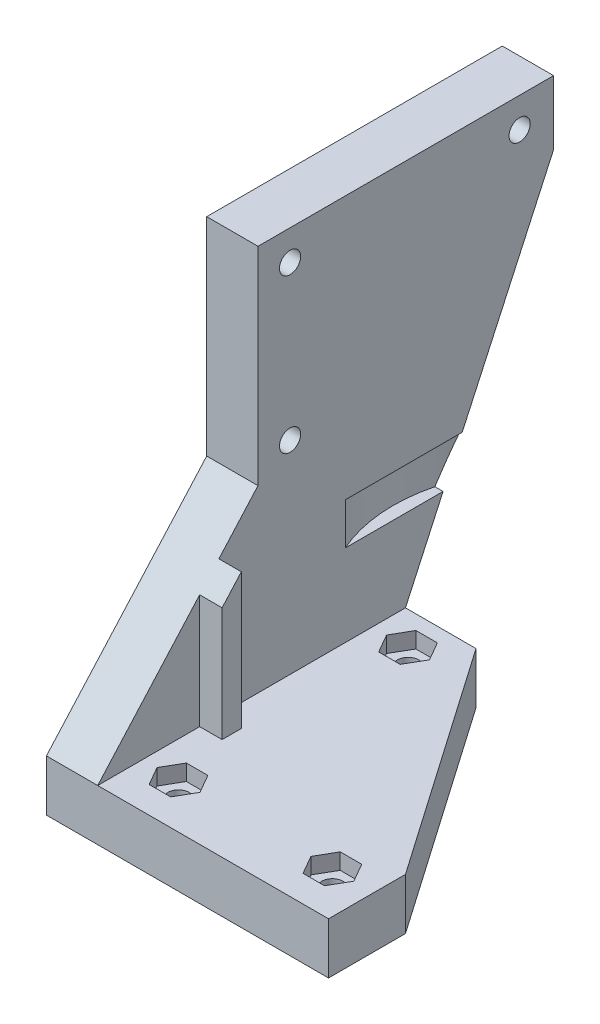
SolidWorks part; units mm, degrees
material "Copper"
ref_plane "Front Plane" through (0, 0, 0) normal (0, 0, 1) x (1, 0, 0)
ref_plane "Top Plane" through (0, 0, 0) normal (0, 1, 0) x (1, 0, 0)
ref_plane "Right Plane" through (0, 0, 0) normal (1, 0, 0) x (0, 0, -1)
sketch "Sketch1" plane through (0, 0, 0) normal (0, 1, 0) x (1, 0, 0)
  line L0 (-30.2016, 21.4588) -> (-19.2016, 21.4588)
  line L1 (5.7984, -26.5412) -> (5.7984, -14.5412)
  line L2 (-30.2016, 21.4588) -> (-30.2016, -26.5412)
  line L3 (-30.2016, -26.5412) -> (5.7984, -26.5412)
  line L4 (5.7984, -14.5412) -> (-19.2016, 21.4588)
  circle A0 centre (-24.6516, 16.3088) radius 1.65
  circle A1 centre (-24.6516, -19.4912) radius 1.65
  circle A2 centre (-0.6516, -19.4912) radius 1.65
  dimension "D3" = 3.3
  dimension "D6" = 3.3
  dimension "D9" = 3.3
  dimension "D1" = 48
  dimension "D2" = 5.15
  dimension "D4" = 5.55
  dimension "D5" = 11
  dimension "D7" = 35.8
  dimension "D8" = 5.55
  dimension "D10" = 24
  dimension "D11" = 35.8
  dimension "D12" = 12
extrude "Boss-Extrude1" add sketch "Sketch1" along normal blind 8
sketch "Sketch3" plane through (-30.2016, 0, 0) normal (-1, 0, 0) x (0, 0, 1)
  line L0 (-21.4588, 8) -> (26.5412, 8) construction
  line L1 (-44.5588, 58.3345) -> (-21.4588, 8)
  line L5 (26.5412, 8) -> (26.5412, 0) construction
  line L7 (-21.4588, 0) -> (26.5412, 0)
  line L8 (26.5412, 0) -> (26.5412, 8)
  line L9 (26.5412, 8) -> (1.5412, 36)
  line L10 (1.5412, 36) -> (1.5412, 68.3345)
  line L11 (1.5412, 68.3345) -> (-44.5588, 68.3345)
  line L12 (-44.5588, 68.3345) -> (-44.5588, 58.3345)
  line L14 (-21.4588, 8) -> (-21.4588, 0)
  circle A0 centre (-3.4588, 39.65) radius 1.65
  circle A1 centre (-3.4588, 63.65) radius 1.65
  circle A2 centre (-39.2588, 63.6645) radius 1.65
  dimension "D1" = 3.3
  dimension "D4" = 3.3
  dimension "D6" = 3.3
  dimension "D2" = 31.65
  dimension "D3" = 30
  dimension "D5" = 24
  dimension "D7" = 35.8
  dimension "D9" = 28
  dimension "D10" = 5
  dimension "D11" = 5.3
  dimension "D12" = 10
  dimension "D13" = 0
  dimension "D14" = 4.67
ref_axis "Axis1" through (-24.6516, 8, 19.4912) along (0, -1, 0)
extrude "Boss-Extrude2" add sketch "Sketch3" along normal blind 8
sketch "Sketch4" plane through (0, 8, 0) normal (0, 1, 0) x (1, 0, 0)
  line L1 (-26.3266, 13.4076) -> (-22.9766, 13.4076)
  line L2 (-22.9766, 13.4076) -> (-21.3016, 16.3088)
  line L3 (-21.3016, 16.3088) -> (-22.9766, 19.2099)
  line L4 (-22.9766, 19.2099) -> (-26.3266, 19.2099)
  line L5 (-26.3266, 19.2099) -> (-28.0016, 16.3088)
  line L6 (-28.0016, 16.3088) -> (-26.3266, 13.4076)
  line L7 (-22.9766, -16.5901) -> (-26.3266, -16.5901)
  line L8 (-26.3266, -16.5901) -> (-28.0016, -19.4912)
  line L9 (-28.0016, -19.4912) -> (-26.3266, -22.3924)
  line L10 (-26.3266, -22.3924) -> (-22.9766, -22.3924)
  line L11 (-22.9766, -22.3924) -> (-21.3016, -19.4912)
  line L12 (-21.3016, -19.4912) -> (-22.9766, -16.5901)
  line L13 (1.0234, -16.5901) -> (-2.3266, -16.5901)
  line L14 (-2.3266, -16.5901) -> (-4.0016, -19.4912)
  line L15 (-4.0016, -19.4912) -> (-2.3266, -22.3924)
  line L16 (-2.3266, -22.3924) -> (1.0234, -22.3924)
  line L17 (1.0234, -22.3924) -> (2.6984, -19.4912)
  line L18 (2.6984, -19.4912) -> (1.0234, -16.5901)
  circle A0 centre (-24.6516, 16.3088) radius 2.9012 construction
  circle A1 centre (-24.6516, -19.4912) radius 2.9012 construction
  circle A2 centre (-0.6516, -19.4912) radius 2.9012 construction
  dimension "D1" = 3.35
  dimension "D2" = 3.35
  dimension "D3" = 3.35
extrude "Cut-Extrude1" cut sketch "Sketch4" against normal blind 2.5
sketch "Sketch5" plane through (-30.2016, 0, 0) normal (1, 0, 0) x (0, 0, -1)
  line L0 (21.4588, 8) -> (-26.5412, 8) construction
  line L1 (-10.6412, 8) -> (-7.6412, 8)
  line L2 (-10.6412, 8) -> (-10.6412, 25.808)
  line L3 (-10.6412, 25.808) -> (-7.6412, 29.168)
  line L4 (-7.6412, 8) -> (-7.6412, 29.168)
  line L5 (-26.5412, 8) -> (-1.5412, 36) construction
  circle A0 centre (3.4588, 39.65) radius 1.65 construction
  dimension "D1" = 11.1
  dimension "D2" = 3
extrude "Boss-Extrude3" add sketch "Sketch5" along direction (1, 0, 0) on the side of the normal blind 3.5
ref_plane "Plane1" through (0, 0, -21.5588) normal (0, 0, -1) x (-1, 0, 0)
ref_plane "Plane2" through (-8.7016, 0, 0) normal (1, 0, 0) x (0, 0, -1)
ref_axis "Axis2" through (-8.7016, 4.9833, -21.5588) along (0, 1, 0)
sketch "Sketch6" plane through (0, 0, -21.5588) normal (0, 0, -1) x (-1, 0, 0)
  line L0 (8.7016, 4.9833) -> (8.7016, 71.3513) construction
  line L1 (8.7016, 20.7845) -> (32.2016, 20.7845)
  line L2 (8.7016, 20.7845) -> (8.7016, 27.2845)
  line L3 (8.7016, 27.2845) -> (32.2016, 27.2845)
  line L4 (32.2016, 20.7845) -> (32.2016, 27.2845)
  line L5 (38.2016, 68.3345) -> (30.2016, 68.3345) construction
  dimension "D1" = 23.5
  dimension "D2" = 6.5
  dimension "D3" = 0
  dimension "D4" = 41.05
revolve "Cut-Revolve1" cut sketch "Sketch6" angle 360 about axis through (-8.7016, 4.9833, -21.5588) along (0, 1, 0)
